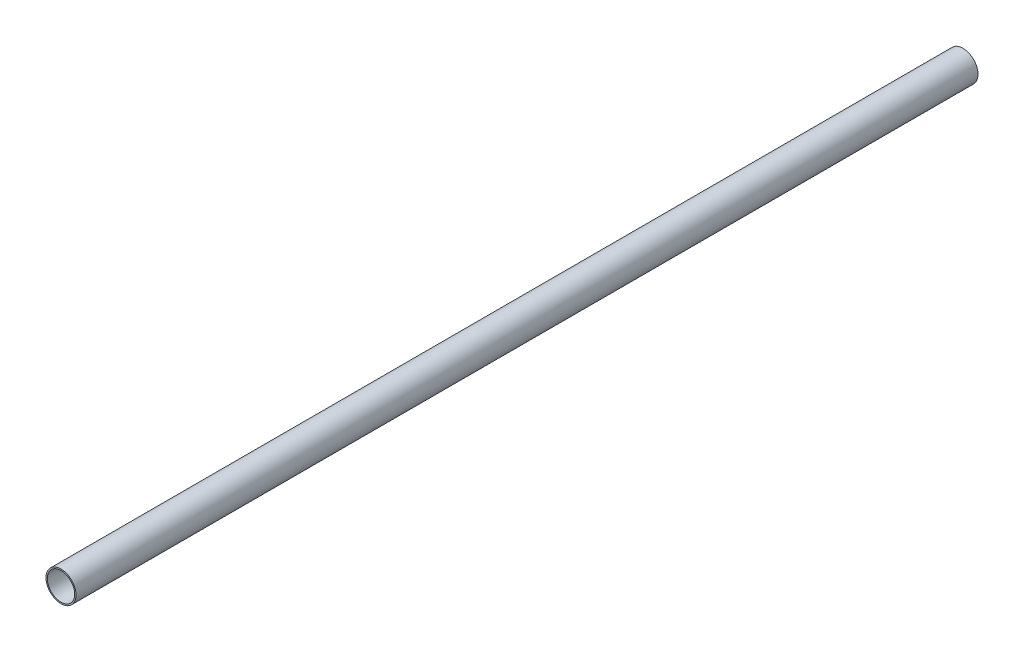
SolidWorks part; units mm, degrees
ref_plane "Front Plane" through (0, 0, 0) normal (0, 0, 1) x (1, 0, 0)
ref_plane "Top Plane" through (0, 0, 0) normal (0, 1, 0) x (1, 0, 0)
ref_plane "Right Plane" through (0, 0, 0) normal (1, 0, 0) x (0, 0, -1)
sketch "Sketch1" plane through (0, 0, 0) normal (0, 0, 1) x (1, 0, 0)
  line L0 (5, 0) -> (4.55, 0) construction
  line L1 (-5, 0) -> (5, 0) construction
  dimension "OD" = 10
  dimension "Wall Thickness" = 0.45
sketch "Sketch2" plane through (0, 0, 0) normal (1, 0, 0) x (0, 0, -1)
  line L0 (150, 0) -> (-150, 0)
  point P4 (0, 0)
  dimension "Length" = 300
sketch "Sketch3" plane through (0, 0, 0) normal (0, 0, 1) x (1, 0, 0)
  circle A0 centre (0, 0) radius 5
  circle A1 centre (0, 0) radius 4.55
extrude "Boss-Extrude1" add sketch "Sketch3" along normal up to vertex (150 mm away) and the other way up to vertex (150 mm away) up to point (0, 0, 150) other way up to point (0, 0, -150)
